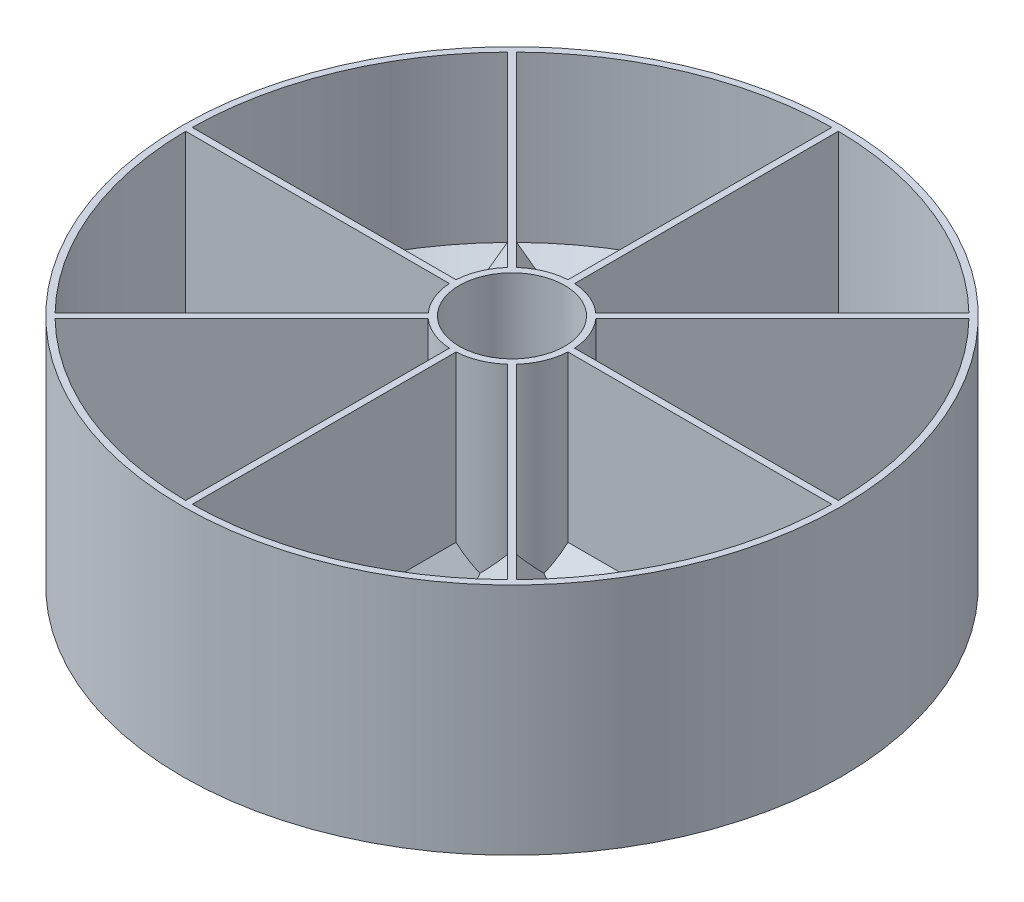
SolidWorks part; units mm, degrees
material "1.4000 (X6Cr13)"
ref_plane "Front Plane" through (0, 0, 0) normal (0, 0, 1) x (1, 0, 0)
ref_plane "Top Plane" through (0, 0, 0) normal (0, 1, 0) x (1, 0, 0)
ref_plane "Right Plane" through (0, 0, 0) normal (1, 0, 0) x (0, 0, -1)
sketch "Sketch1" plane through (0, 0, 0) normal (0, 1, 0) x (1, 0, 0)
  circle A0 centre (0, 0) radius 100
  dimension "D1" = 200
sketch "Sketch2" plane through (0, 0, 0) normal (0, 1, 0) x (1, 0, 0)
  circle A0 centre (0, 0) radius 100
  circle A1 centre (0, 0) radius 98
  dimension "D1" = 196
extrude "Boss-Extrude2" add sketch "Sketch2" along normal blind 70
sketch "Sketch3" plane through (0, 0, 0) normal (0, 1, 0) x (1, 0, 0)
  circle A0 centre (0, 0) radius 18
  circle A1 centre (0, 0) radius 16
  dimension "D1" = 36
  dimension "D2" = 32
extrude "Boss-Extrude3" add sketch "Sketch3" along normal blind 70
sketch "Sketch4" plane through (0, 0, 0) normal (0, 1, 0) x (1, 0, 0)
  line L0 (0, -18) -> (0, -98) construction
  line L1 (-1, -17.9722) -> (-1, -97.9949)
  line L2 (1, -17.9722) -> (1, -97.9949)
  arc A2 (1, -17.9722) -> (-1, -17.9722) centre (0, 0) cw
  arc A3 (1, -97.9949) -> (-1, -97.9949) centre (0, 0) cw
  circle A4 centre (0, 0) radius 18 construction
  circle A5 centre (0, 0) radius 98 construction
  dimension "D1" = 1
  dimension "D2" = 1
extrude "Boss-Extrude4" add sketch "Sketch4" along normal blind 70 contours L0 A2 L1 | L0 A3 L2 region at (0, 0, 57.9945)
pattern_circular "CirPattern1" count 8 over 360 about axis through (0, 70, 0) along (0, -1, 0) of "Boss-Extrude4" reverse direction yes
sketch "Sketch5" plane through (0, 0, 0) normal (0, -1, 0) x (1, 0, 0)
  circle A0 centre (0, 0) radius 100
extrude "Boss-Extrude5" add sketch "Sketch5" along normal blind 1
sketch "Sketch6" plane through (0, 0, 0) normal (0, 1, 0) x (1, 0, 0)
  line L0 (-13.4154, -12.0012) -> (-70, -68.5857) construction
  line L1 (-97.9949, -1) -> (-57.9949, -1)
  line L2 (-17.9722, -1) -> (-97.9949, -1) construction
  line L3 (-70, -68.5857) -> (-41.7157, -40.3015)
  arc A0 (-97.9949, -1) -> (-70, -68.5857) centre (0, 0) ccw
  arc A1 (-57.9949, -1) -> (-41.7157, -40.3015) centre (0, 0) ccw
  dimension "D1" = 40
extrude "Cut-Extrude1" [suppressed] cut sketch "Sketch6" against normal blind 2
sketch "Sketch9" plane through (0, 0, 0) normal (0, 1, 0) x (1, 0, 0)
  circle A0 centre (0, 0) radius 16
extrude "Boss-Extrude6" add sketch "Sketch9" along normal blind 10
sketch "Sketch10" plane through (0, 10, 0) normal (0, 1, 0) x (1, 0, 0)
  line L1 (0, 16) -> (-13.8564, 8)
  line L2 (-13.8564, 8) -> (-13.8564, -8)
  line L3 (-13.8564, -8) -> (0, -16)
  line L4 (0, -16) -> (13.8564, -8)
  line L5 (13.8564, -8) -> (13.8564, 8)
  line L6 (13.8564, 8) -> (0, 16)
  circle A0 centre (0, 0) radius 16 construction
extrude "Cut-Extrude2" cut sketch "Sketch10" against normal through all
chamfer "Chamfer1" distance 20 angle 45 32 edges at (-6.8883, 0, -16.6298) (-16.6298, 0, -6.8883) (-16.6298, 0, 6.8883) (-6.8883, 0, 16.6298) (6.8883, 0, 16.6298) (16.6298, 0, 6.8883) (16.6298, 0, -6.8883) (6.8883, 0, -16.6298) (-57.9835, 0, -1) (-90.5402, 0, -37.503) (-41.7077, 0, -40.2935) (-40.2935, 0, -41.7077) (-37.503, 0, -90.5402) (-1, 0, -57.9835) (1, 0, -57.9835) (37.503, 0, -90.5402) (40.2935, 0, -41.7077) (41.7077, 0, -40.2935) (90.5402, 0, -37.503) (57.9835, 0, -1) (57.9835, 0, 1) (90.5402, 0, 37.503) (41.7077, 0, 40.2935) (40.2935, 0, 41.7077) (37.503, 0, 90.5402) (1, 0, 57.9835) (-41.7077, 0, 40.2935) (-90.5402, 0, 37.503) (-57.9835, 0, 1) (-40.2935, 0, 41.7077) (-37.503, 0, 90.5402) (-1, 0, 57.9835)
sketch "Sketch11" plane through (0, 0, 0) normal (0, 1, 0) x (1, 0, 0)
  line L0 (-21, -50.6985) -> (-38.2686, -67.967)
  line L1 (-38.2686, -67.967) -> (-21, -75.1199)
  line L2 (-21, -75.1199) -> (-21, -50.6985)
extrude "Cut-Extrude3" cut sketch "Sketch11" against normal through all
pattern_circular "CirPattern2" count 8 over 360 about axis through (0, 70, 0) along (0, -1, 0) of "Cut-Extrude3" reverse direction yes
